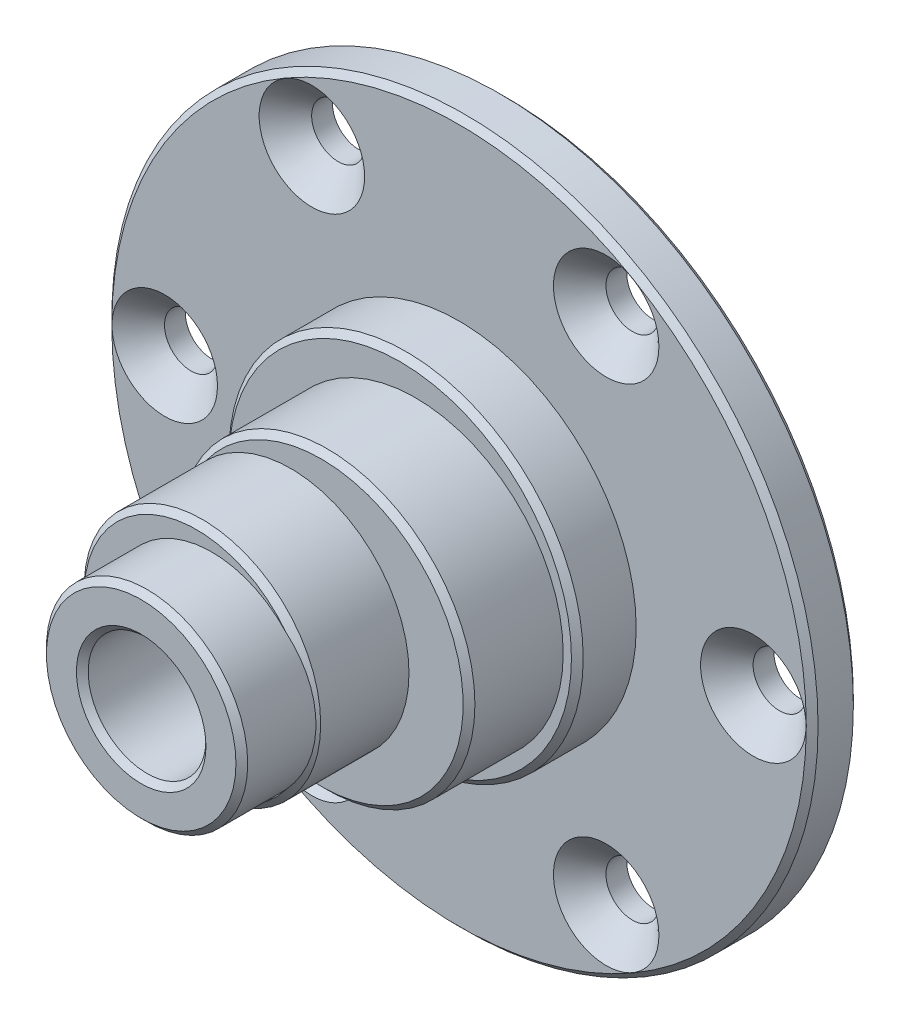
SolidWorks part; units mm, degrees
material "6061-T6 (SS)"
ref_plane "Front Plane" through (0, 0, 0) normal (0, 0, 1) x (1, 0, 0)
ref_plane "Top Plane" through (0, 0, 0) normal (0, 1, 0) x (1, 0, 0)
ref_plane "Right Plane" through (0, 0, 0) normal (1, 0, 0) x (0, 0, -1)
sketch "Sketch1" plane through (0, 0, 0) normal (0, 0, 1) x (1, 0, 0)
  circle A0 centre (0, 0) radius 30 construction
  circle A1 centre (0, 0) radius 30
extrude "Boss-Extrude1" add sketch "Sketch1" along normal blind 4
sketch "Sketch2" plane through (0, 0, 4) normal (0, 0, 1) x (1, 0, 0)
  line L0 (0, 0) -> (0, 25) construction
  line L1 (0, 0) -> (-12.5, 21.6506) construction
  circle A0 centre (0, 0) radius 25 construction
  arc A3 (-44.5, 0) -> (44.5, 0) centre (0, 0) ccw
  arc A4 (44.5, 0) -> (-44.5, 0) centre (0, 0) ccw
  arc A5 (-44.5, 0) -> (44.5, 0) centre (0, 0) ccw
  arc A6 (44.5, 0) -> (-44.5, 0) centre (0, 0) ccw
  circle A11 centre (0, 0) radius 15.05
  circle A12 centre (0, 0) radius 10.05
  point P10 (-12.5, 21.6506)
  point P12 (12.5, 21.6506)
  point P13 (25, 0)
  point P14 (12.5, -21.6506)
  point P15 (-12.5, -21.6506)
  point P16 (-25, 0)
  point P17 (0, 0)
  point P22 (0, 0)
  dimension "D1" = 50
  dimension "D4" = 6
  dimension "D5" = 30.1
  dimension "D3" = 30
  dimension "D2" = 0
  dimension "D6" = 5
hole_wizard "CSK for M4 Hex Socket Countersunk Cap Screw1" positions "Sketch4" profile "Sketch3" countersink size "M4" standard "ISO" end condition through all
sketch "Sketch4" plane through (0, 0, 4) normal (0, 0, 1) x (1, 0, 0)
  point P4 (-12.5, 21.6506)
  point P7 (12.5, 21.6506)
  point P10 (25, 0)
  point P13 (-12.5, -21.6506)
  point P16 (12.5, -21.6506)
  point P19 (-25, 0)
sketch "Sketch3" plane through (-12.5, 21.6506, 4) normal (1, 0, 0) x (0, -1, 0)
  line L0 (0, 0) -> (0, 4)
  line L1 (0, 4) -> (2.25, 4)
  line L2 (2.25, 4) -> (2.25, 2.23)
  line L3 (2.25, 2.23) -> (4.48, 0)
  line L5 (4.48, 0) -> (0, 0)
  line L6 (-2.25, 2.23) -> (-4.48, 0) construction
  line L11 (0, -6.35) -> (0, 107.95) construction
  dimension "Thru Hole Dia." = 4.5
  dimension "Thru Hole Depth" = 4
  dimension "Near C'Sink Dia." = 8.96
  dimension "Near C'Sink Angle" = 90
extrude "Boss-Extrude3" add sketch "Sketch2" along normal blind 5 contours A11 A12 region at (-14.6243, 0, 4)
sketch "Sketch5" plane through (0, 0, 0) normal (0, 0, -1) x (-1, 0, 0)
  circle A0 centre (0, 0) radius 12
  dimension "D1" = 24
extrude "Cut-Extrude2" cut sketch "Sketch5" against normal blind 4
sketch "Sketch6" plane through (0, 0, 9) normal (0, 0, 1) x (1, 0, 0)
  circle A0 centre (1.3, 0) radius 12.55
  dimension "D1" = 25.1
  dimension "D2" = 1.3
extrude "Boss-Extrude4" add sketch "Sketch6" along normal blind 8
sketch "Sketch7" plane through (0, 0, 17) normal (0, 0, 1) x (1, 0, 0)
  circle A0 centre (-1.3, 0) radius 10.05
  dimension "D1" = 20.1
  dimension "D2" = 1.3
extrude "Boss-Extrude5" add sketch "Sketch7" along normal blind 8
sketch "Sketch8" plane through (0, 0, 25) normal (0, 0, 1) x (1, 0, 0)
  circle A0 centre (0, 0) radius 8.55
  dimension "D1" = 17.1
extrude "Boss-Extrude6" add sketch "Sketch8" along normal blind 6
sketch "Sketch9" plane through (0, 0, 31) normal (0, 0, 1) x (1, 0, 0)
  circle A0 centre (0, 0) radius 5
  dimension "D1" = 10
extrude "Cut-Extrude3" cut sketch "Sketch9" against normal blind 30
chamfer "Chamfer1" distance 0.5 angle 45 9 edges at (10.05, 0, 4) (-12, 0, 0) (5, 0, 31) (30, 0, 0) (30, 0, 4) (15.05, 0, 9) (13.85, 0, 17) (8.75, 0, 25) (8.55, 0, 31)
